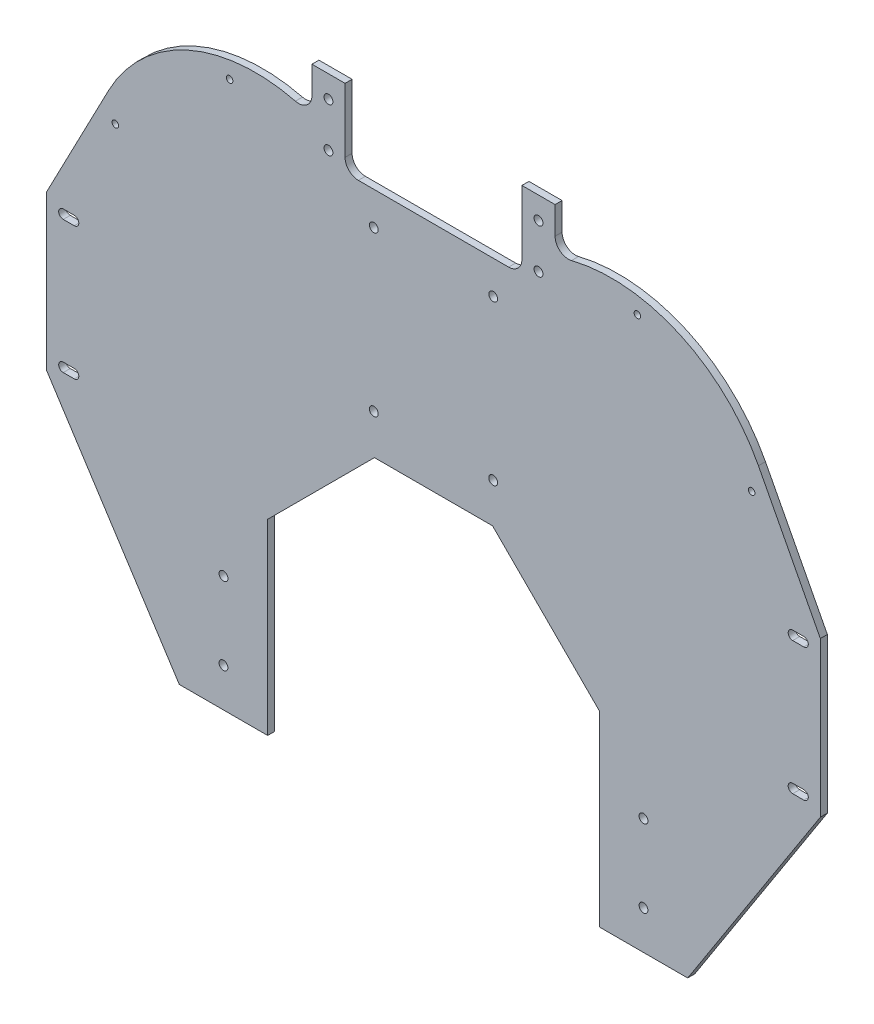
SolidWorks part; units mm, degrees
ref_plane "Front Plane" through (0, 0, 0) normal (0, 0, 1) x (1, 0, 0)
ref_plane "Top Plane" through (0, 0, 0) normal (0, 1, 0) x (1, 0, 0)
ref_plane "Right Plane" through (0, 0, 0) normal (1, 0, 0) x (0, 0, -1)
sketch "Sketch1" plane through (0, 0, 0) normal (0, 0, 1) x (1, 0, 0)
  line L1 (-100, -75) -> (100, -75)
  line L2 (-100, -75) -> (-100, 75)
  line L3 (-100, 75) -> (100, 75)
  line L4 (100, -75) -> (100, 75)
  line L5 (-100, -75) -> (100, 75) construction
  line L6 (-100, 75) -> (100, -75) construction
  line L8 (-47.5, 40) -> (47.5, 40) construction
  line L9 (0, 75) -> (0, -75) construction
  line L10 (-27, -52) -> (27, -52) construction
  line L11 (-27, -52) -> (-27, 20) construction
  line L12 (-27, 20) -> (27, 20) construction
  line L13 (27, -52) -> (27, 20) construction
  line L14 (-27, -52) -> (27, 20) construction
  line L15 (-27, 20) -> (27, -52) construction
  line L23 (-55, 70) -> (55, 70)
  line L24 (-55, 70) -> (-55, -70)
  line L25 (-55, -70) -> (55, -70)
  line L26 (55, 70) -> (55, -70)
  line L27 (-55, 70) -> (55, -70) construction
  line L28 (-55, -70) -> (55, 70) construction
  line L29 (-40, 70) -> (40, 70)
  line L30 (-40, 70) -> (-40, 35)
  line L31 (-40, 35) -> (40, 35)
  line L32 (40, 70) -> (40, 35)
  line L33 (-40, 70) -> (40, 35) construction
  line L34 (-40, 35) -> (40, 70) construction
  circle A2 centre (-47.5, 40) radius 2
  circle A3 centre (47.5, 40) radius 2
  circle A4 centre (-27, 20) radius 2
  circle A5 centre (27, 20) radius 2
  circle A6 centre (27, -52) radius 2
  circle A7 centre (-27, -52) radius 2
  circle A8 centre (-47.5, 60) radius 2
  circle A9 centre (47.5, 60) radius 2
  point P0 (0, 0)
  point P15 (0, 40)
  point P18 (0, -16)
  point P56 (0, 0)
  point P63 (0, 52.5)
  dimension "D3" = 4
  dimension "D4" = 20
  dimension "D5" = 4
  dimension "D8" = 4
  dimension "D1" = 150
  dimension "D2" = 200
  dimension "D6" = 72
  dimension "D7" = 54
  dimension "D14" = 30
  dimension "D15" = 140
  dimension "D16" = 110
  dimension "D17" = 95
  dimension "D18" = 20
  dimension "D19" = 35
  dimension "D20" = 80
extrude "Boss-Extrude1" add sketch "Sketch1" along normal blind 3.175 contours L23 L32 L31 L30 L24 L25 L26 A7 A6 A5 A4 A3 A2 region at (0, -11.8972, 0)
sketch "Sketch2" plane through (0, 0, 0) normal (0, 0, 1) x (1, 0, 0)
  line L0 (-55, -70) -> (-100.8579, -115.8579) construction
  line L1 (-55, 70) -> (-55, -70) construction
  line L2 (-55, -41.7157) -> (-115, -101.7157)
  line L3 (-26.7157, -70) -> (-86.7157, -130)
  line L4 (-55, -70) -> (55, -70) construction
  line L5 (-115, -101.7157) -> (-86.7157, -130)
  line L6 (-115, -101.7157) -> (-115, -203)
  line L7 (-75, -118.2843) -> (-75, -203)
  line L8 (-75, -203) -> (-115, -203)
  line L9 (0, 75) -> (0, -75) construction
  line L10 (-55, -41.7157) -> (-26.7157, -70)
  line L11 (-55, 70) -> (-55, -70) construction
  line L12 (-75, -203) -> (-115, -203) construction
  line L13 (-55, -70) -> (55, -70) construction
  line L14 (-55, 70) -> (-55, -70) construction
  circle A0 centre (-95, -150.5) radius 2
  circle A1 centre (-95, -185.5) radius 2
  dimension "D5" = 4
  dimension "D6" = 4
  dimension "D1" = 135
  dimension "D2" = 40
  dimension "D3" = 40
  dimension "D4" = 75
extrude "Boss-Extrude2" add sketch "Sketch2" along normal blind 3.175 contours L8 L7 L3 L5 L6 | L10 L2 L5 L3 region at (-70.8579, -85.8579, 0) region at (-95.9289, -160.2024, 0)
mirror "Mirror1" about plane through (0, 0, 0) normal (1, 0, 0) of "Boss-Extrude2"
sketch "Sketch3" plane through (0, 0, 3.175) normal (0, 0, 1) x (1, 0, 0)
  line L0 (0, 0) -> (0, 95.843) construction
  line L1 (-80.5, -21) -> (-92.2213, 45.4745) construction
  line L2 (-80.5, -21) -> (-143.9293, 2.0864) construction
  line L3 (-80.5, -21) -> (-148, -21) construction
  line L4 (-42.1979, -85.4821) -> (-26.7157, -70)
  line L5 (-26.7157, -70) -> (-23.7197, -70)
  line L6 (-26.7157, -70) -> (26.7157, -70) construction
  line L7 (-26.7157, -70) -> (-75, -118.2843) construction
  line L8 (26.7157, -70) -> (23.7197, -70)
  line L9 (42.1979, -85.4821) -> (26.7157, -70)
  circle A0 centre (-80.5, -21) radius 60 construction
  circle A1 centre (-80.5, -21) radius 75
  circle A2 centre (-80.5, -21) radius 67.5 construction
  circle A3 centre (-92.2213, 45.4745) radius 1.4732
  circle A4 centre (-143.9293, 2.0864) radius 1.4732
  circle A5 centre (-47.5, 40) radius 2 construction
  circle A6 centre (143.9293, 2.0864) radius 1.4732
  circle A7 centre (92.2213, 45.4745) radius 1.4732
  circle A8 centre (80.5, -21) radius 75
  circle A9 centre (-47.5, 40) radius 2
  circle A10 centre (-27, 20) radius 2
  circle A11 centre (-27, -52) radius 2
  circle A12 centre (-27, 20) radius 2 construction
  circle A13 centre (-27, -52) radius 2 construction
  circle A14 centre (47.5, 40) radius 2
  circle A15 centre (27, 20) radius 2
  circle A16 centre (27, -52) radius 2
  line M5 (-26.7157, -70) -> (26.7157, -70)
  line M6 (26.7157, -70) -> (75, -118.2843)
  line M10 (115, -101.7157) -> (55, -41.7157)
  line M11 (55, -41.7157) -> (55, 70)
  line M13 (40, 70) -> (40, 35)
  line M14 (40, 35) -> (-40, 35)
  line M15 (-40, 35) -> (-40, 70)
  line M17 (-55, 70) -> (-55, -41.7157)
  line M18 (-55, -41.7157) -> (-115, -101.7157)
  line M22 (-75, -118.2843) -> (-26.7157, -70)
  circle M23 centre (-47.5, 40) radius 2
  circle M24 centre (47.5, 40) radius 2
  circle M25 centre (-27, 20) radius 2
  circle M26 centre (27, 20) radius 2
  circle M27 centre (27, -52) radius 2
  circle M28 centre (-27, -52) radius 2
  dimension "D1" = 120
  dimension "D3" = 7.5
  dimension "D4" = 61
  dimension "D8" = 2.9464
  dimension "D5" = 80
  dimension "D6" = 20
  dimension "D7" = 161
  dimension "D2" = 15
extrude "Boss-Extrude3" add sketch "Sketch3" against normal up to surface (3.175 mm away) contours A1 A4 A3 M17 M18 | A1 M15 M17 M18 M22 M5 M14 M28 M25 M23 | A8 M10 M11 M13 M14 M5 M6 M27 M26 M24 | A8 A6 A7 M11 M10 region at (-42.8459, -33.3688, 3.175) region at (-102.3675, -14.0811, 3.175) region at (42.8459, -33.3688, 3.175) region at (102.3675, -14.0811, 3.175) up to face at (0, -62.524, 0)
sketch "Sketch4" plane through (0, 0, 3.175) normal (0, 0, 1) x (1, 0, 0)
  line L0 (-175, -110) -> (-115, -203)
  line L1 (-100, -110) -> (-115, -110) construction
  line L2 (-100, -110) -> (-100, -40)
  line L3 (-100, -40) -> (-152.4428, -40)
  line L4 (-175, -110) -> (-175, -40)
  line L5 (-100, -110) -> (-175, -40) construction
  line L6 (-100, -40) -> (-175, -110) construction
  line L8 (-115, -101.7157) -> (-115, -203) construction
  line L9 (-115, -110) -> (-115, -203)
  line L10 (-151.1989, -110) -> (-175, -110) construction
  line L11 (-175, -40) -> (-146.9976, 13.6853)
  line L12 (-152.4428, -40) -> (-152.8464, -40.7738)
  line L13 (-152.4428, -40) -> (-175, -40) construction
  line L14 (-175, -75) -> (-100, -75) construction
  line L15 (-165, -40) -> (-165, -75) construction
  line L18 (-100, -110) -> (-100, -101.7157)
  line L19 (-100, -101.7157) -> (-115, -101.7157)
  line L20 (-115, -110) -> (-115, -101.7157)
  line L21 (-100, -110) -> (-115, -101.7157) construction
  line L22 (-100, -101.7157) -> (-115, -110) construction
  line L23 (-162.5, -45) -> (-167.5, -45) construction
  line L24 (-162.5, -47.05) -> (-167.5, -47.05)
  line L25 (-162.5, -42.95) -> (-167.5, -42.95)
  line L26 (-162.5, -105) -> (-167.5, -105) construction
  line L27 (-162.5, -102.95) -> (-167.5, -102.95)
  line L28 (-162.5, -107.05) -> (-167.5, -107.05)
  circle A0 centre (-143.9293, 2.0864) radius 1.4732
  circle A1 centre (-143.9293, 2.0864) radius 1.4732 construction
  arc A2 (-55, 49.5319) -> (-105.1261, -91.8418) centre (-80.5, -21) ccw construction
  arc A3 (-152.8464, -40.7738) -> (-146.9976, 13.6853) centre (-80.5, -21) cw
  circle A4 centre (-165, -45) radius 2.05 construction
  circle A6 centre (-165, -105) radius 2.05 construction
  arc A7 (-162.5, -47.05) -> (-162.5, -42.95) centre (-162.5, -45) ccw
  arc A8 (-167.5, -42.95) -> (-167.5, -47.05) centre (-167.5, -45) ccw
  arc A9 (-162.5, -102.95) -> (-162.5, -107.05) centre (-162.5, -105) cw
  arc A10 (-167.5, -107.05) -> (-167.5, -102.95) centre (-167.5, -105) cw
  point P0 (-137.5, -75)
  point P31 (-115, -110.8979)
  point P36 (-107.5, -105.8579)
  point P38 (-165, -45)
  point P48 (-165, -105)
  arc M14 (-55, 49.5319) -> (-105.1261, -91.8418) centre (-80.5, -21) ccw
  line M15 (-105.1261, -91.8418) -> (-115, -101.7157)
  line M16 (-115, -101.7157) -> (-115, -203)
  dimension "D7" = 4.1
  dimension "D9" = 2.05
  dimension "D1" = 100
  dimension "D2" = 40
  dimension "D3" = 75
  dimension "D4" = 70
  dimension "D6" = 20
  dimension "D8" = 10
  dimension "D10" = 5
  dimension "D11" = 5
extrude "Boss-Extrude4" add sketch "Sketch4" against normal up to surface (3.175 mm away) contours L11 L4 L0 A8 L25 A7 L24 L28 A10 L27 A9 M16 M15 M14 region at (-143.8938, -104.7844, 3.175) up to face at (0, -53.8091, 0)
mirror "Mirror2" about plane through (0, 0, 0) normal (1, 0, 0) of "Boss-Extrude4"
fillet "Fillet1" radius 6 4 edges at (-55, 49.5319, 1.5875) (-40, 35, 1.5875) (40, 35, 1.5875) (55, 49.5319, 1.5875)
